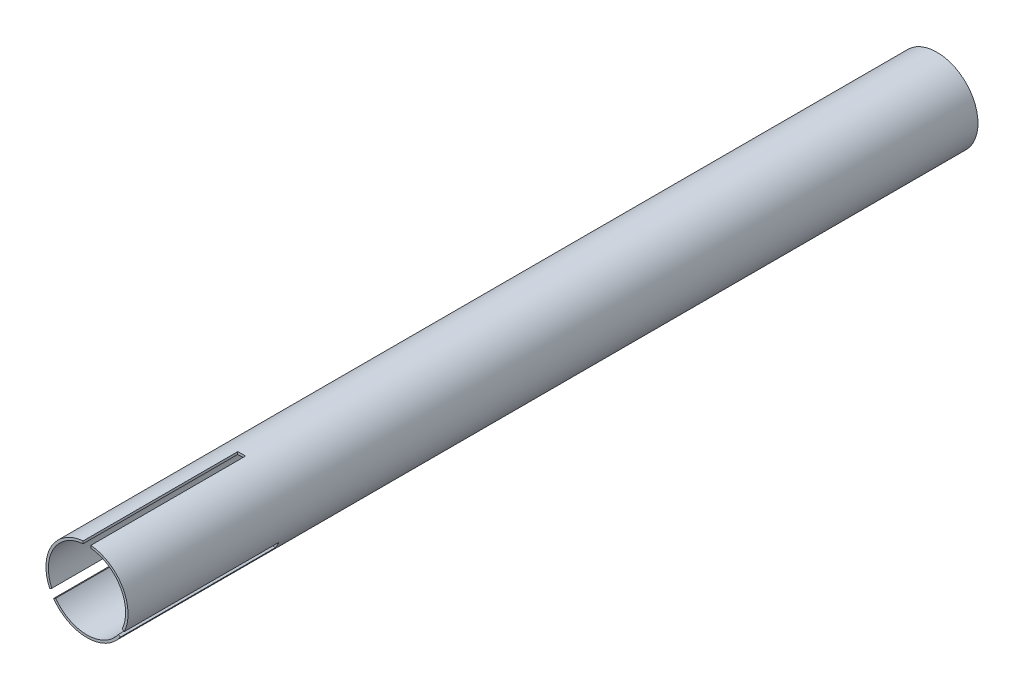
SolidWorks part; units mm, degrees
material "Corrugated Paper"
ref_plane "Front Plane" through (0, 0, 0) normal (0, 0, 1) x (1, 0, 0)
ref_plane "Top Plane" through (0, 0, 0) normal (0, 1, 0) x (1, 0, 0)
ref_plane "Right Plane" through (0, 0, 0) normal (1, 0, 0) x (0, 0, -1)
sketch "Sketch1" plane through (0, 0, 0) normal (0, 0, 1) x (1, 0, 0)
  circle A0 centre (0, 0) radius 25.4
  circle A1 centre (0, 0) radius 26.9875
  dimension "D1" = 53.975
  dimension "D2" = 50.8
extrude "Boss-Extrude1" add sketch "Sketch1" along normal blind 558.8
sketch "Sketch2" plane through (0, 0, 0) normal (0, 1, 0) x (1, 0, 0)
  line L0 (-26.9875, -558.8) -> (26.9875, -558.8) construction
  line L1 (-2.54, -558.8) -> (2.54, -558.8)
  line L2 (-2.54, -558.8) -> (-2.54, -457.2)
  line L3 (-2.54, -457.2) -> (2.54, -457.2)
  line L4 (2.54, -558.8) -> (2.54, -457.2)
  point P6 (0, -558.8)
  dimension "D1" = 5.08
  dimension "D2" = 101.6
extrude "Cut-Extrude1" cut sketch "Sketch2" along normal up to next
ref_axis "Axis1" through (0, 0, -27.94) along (0, 0, 1)
pattern_circular "CirPattern1" count 3 every 120 about axis through (0, 0, -27.94) along (0, 0, 1) of "Cut-Extrude1"
